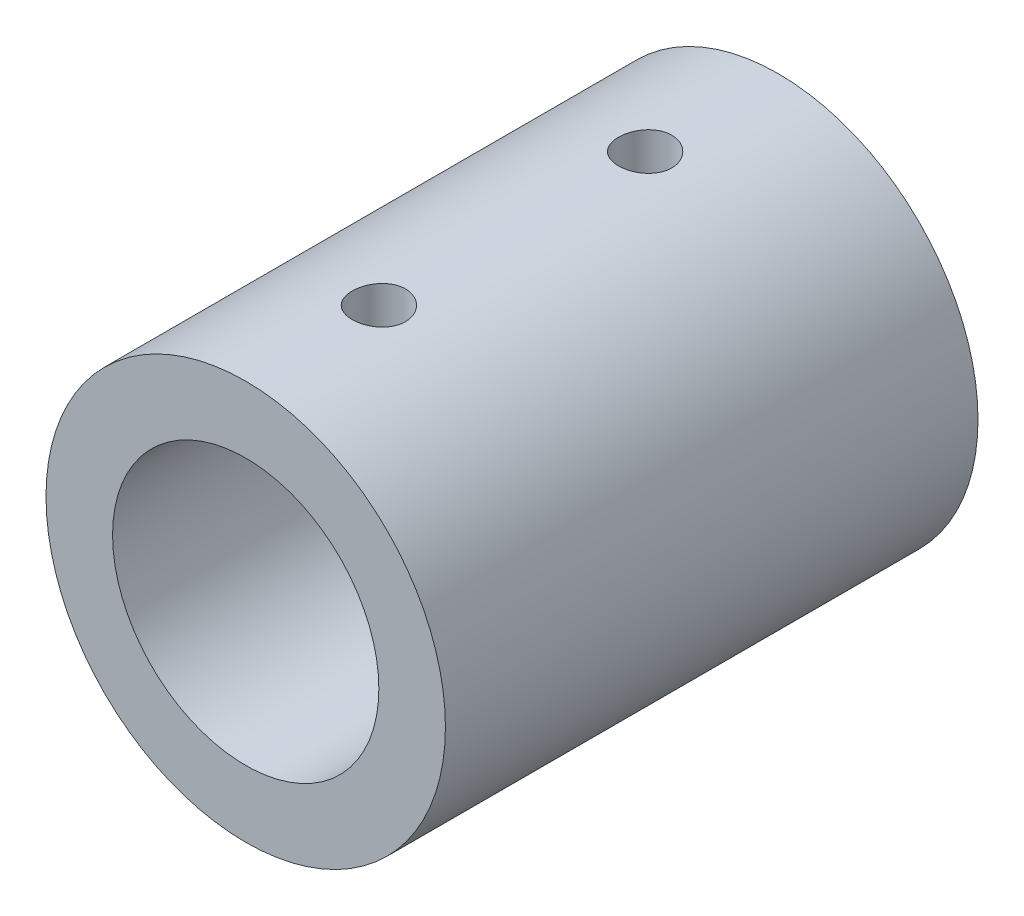
SolidWorks part; units mm, degrees
ref_plane "Front Plane" through (0, 0, 0) normal (0, 0, 1) x (1, 0, 0)
ref_plane "Top Plane" through (0, 0, 0) normal (0, 1, 0) x (1, 0, 0)
ref_plane "Right Plane" through (0, 0, 0) normal (1, 0, 0) x (0, 0, -1)
sketch "Sketch1" plane through (0, 0, 0) normal (0, 0, 1) x (1, 0, 0)
  circle A0 centre (0, 0) radius 15
  circle A1 centre (0, 0) radius 22.5
  dimension "D1" = 30
  dimension "D2" = 7.5
extrude "Boss-Extrude1" add sketch "Sketch1" along normal blind 30 and the other way blind 30
sketch "Sketch2" plane through (0, 0, 0) normal (0, 1, 0) x (1, 0, 0)
  circle A0 centre (0, -15) radius 3
  point P2 (0, 0)
  dimension "D1" = 6
  dimension "D2" = 15
extrude "Cut-Extrude1" cut sketch "Sketch2" along normal blind 30
mirror "Mirror1" about plane through (0, 0, 0) normal (0, 0, 1) of "Cut-Extrude1"
